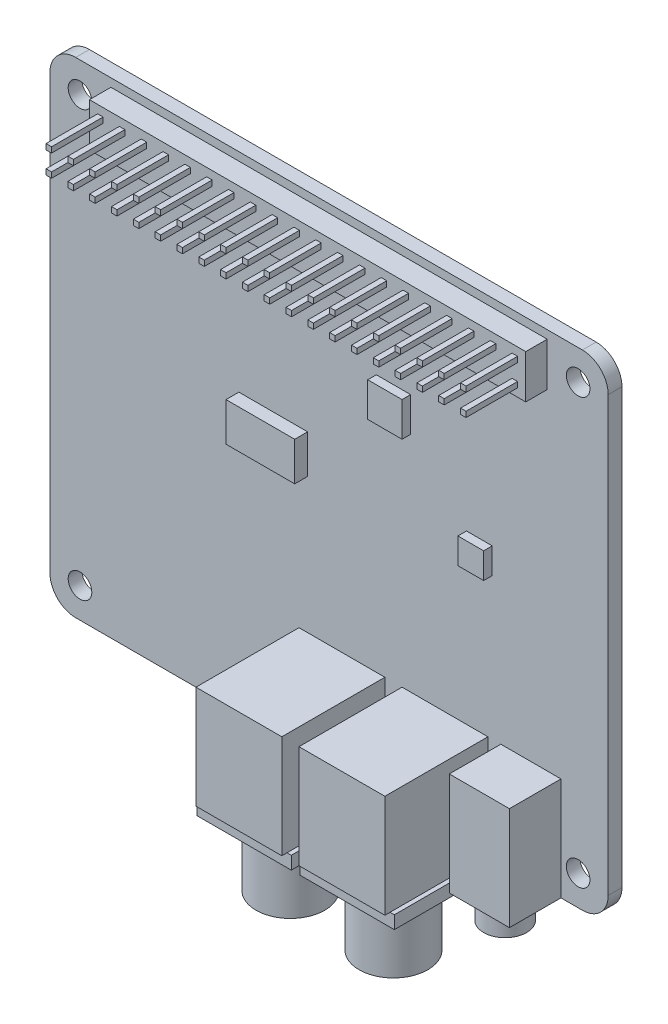
SolidWorks part; units mm, degrees
ref_plane "Front Plane" through (0, 0, 0) normal (0, 0, 1) x (1, 0, 0)
ref_plane "Top Plane" through (0, 0, 0) normal (0, 1, 0) x (1, 0, 0)
ref_plane "Right Plane" through (0, 0, 0) normal (1, 0, 0) x (0, 0, -1)
sketch "Sketch1" plane through (0, 0, 0) normal (0, 0, 1) x (1, 0, 0)
  line L0 (3, 0) -> (62, 0)
  line L1 (65, 3) -> (65, 53.5)
  line L2 (62, 56.5) -> (3, 56.5)
  line L3 (0, 53.5) -> (0, 3)
  arc A0 (62, 0) -> (65, 3) centre (62, 3) ccw
  arc A1 (65, 53.5) -> (62, 56.5) centre (62, 53.5) ccw
  arc A2 (3, 56.5) -> (0, 53.5) centre (3, 53.5) ccw
  arc A3 (0, 3) -> (3, 0) centre (3, 3) ccw
extrude "PCB" add sketch "Sketch1" along normal blind 1.6
ref_plane "Plane_z1_6" through (0, 0, 1.6) normal (0, 0, 1) x (1, 0, 0)
sketch "Sketch2" plane through (0, 0, 1.6) normal (0, 0, 1) x (1, 0, 0)
  line L1 (7.1, 50.46) -> (57.9, 50.46)
  line L2 (7.1, 50.46) -> (7.1, 55.54)
  line L3 (7.1, 55.54) -> (57.9, 55.54)
  line L4 (57.9, 50.46) -> (57.9, 55.54)
extrude "Header_Block" add sketch "Sketch2" along normal blind 2.5
ref_plane "Plane_z4_1" through (0, 0, 4.1) normal (0, 0, 1) x (1, 0, 0)
sketch "Sketch3" plane through (0, 0, 4.1) normal (0, 0, 1) x (1, 0, 0)
  line L1 (8.05, 51.41) -> (8.69, 51.41)
  line L2 (8.05, 51.41) -> (8.05, 52.05)
  line L3 (8.05, 52.05) -> (8.69, 52.05)
  line L4 (8.69, 51.41) -> (8.69, 52.05)
  line L6 (8.05, 53.95) -> (8.69, 53.95)
  line L7 (8.05, 53.95) -> (8.05, 54.59)
  line L8 (8.05, 54.59) -> (8.69, 54.59)
  line L9 (8.69, 53.95) -> (8.69, 54.59)
  line L11 (10.59, 51.41) -> (11.23, 51.41)
  line L12 (10.59, 51.41) -> (10.59, 52.05)
  line L13 (10.59, 52.05) -> (11.23, 52.05)
  line L14 (11.23, 51.41) -> (11.23, 52.05)
  line L16 (10.59, 53.95) -> (11.23, 53.95)
  line L17 (10.59, 53.95) -> (10.59, 54.59)
  line L18 (10.59, 54.59) -> (11.23, 54.59)
  line L19 (11.23, 53.95) -> (11.23, 54.59)
  line L21 (13.13, 51.41) -> (13.77, 51.41)
  line L22 (13.13, 51.41) -> (13.13, 52.05)
  line L23 (13.13, 52.05) -> (13.77, 52.05)
  line L24 (13.77, 51.41) -> (13.77, 52.05)
  line L26 (13.13, 53.95) -> (13.77, 53.95)
  line L27 (13.13, 53.95) -> (13.13, 54.59)
  line L28 (13.13, 54.59) -> (13.77, 54.59)
  line L29 (13.77, 53.95) -> (13.77, 54.59)
  line L31 (15.67, 51.41) -> (16.31, 51.41)
  line L32 (15.67, 51.41) -> (15.67, 52.05)
  line L33 (15.67, 52.05) -> (16.31, 52.05)
  line L34 (16.31, 51.41) -> (16.31, 52.05)
  line L36 (15.67, 53.95) -> (16.31, 53.95)
  line L37 (15.67, 53.95) -> (15.67, 54.59)
  line L38 (15.67, 54.59) -> (16.31, 54.59)
  line L39 (16.31, 53.95) -> (16.31, 54.59)
  line L41 (18.21, 51.41) -> (18.85, 51.41)
  line L42 (18.21, 51.41) -> (18.21, 52.05)
  line L43 (18.21, 52.05) -> (18.85, 52.05)
  line L44 (18.85, 51.41) -> (18.85, 52.05)
  line L46 (18.21, 53.95) -> (18.85, 53.95)
  line L47 (18.21, 53.95) -> (18.21, 54.59)
  line L48 (18.21, 54.59) -> (18.85, 54.59)
  line L49 (18.85, 53.95) -> (18.85, 54.59)
  line L51 (20.75, 51.41) -> (21.39, 51.41)
  line L52 (20.75, 51.41) -> (20.75, 52.05)
  line L53 (20.75, 52.05) -> (21.39, 52.05)
  line L54 (21.39, 51.41) -> (21.39, 52.05)
  line L56 (20.75, 53.95) -> (21.39, 53.95)
  line L57 (20.75, 53.95) -> (20.75, 54.59)
  line L58 (20.75, 54.59) -> (21.39, 54.59)
  line L59 (21.39, 53.95) -> (21.39, 54.59)
  line L61 (23.29, 51.41) -> (23.93, 51.41)
  line L62 (23.29, 51.41) -> (23.29, 52.05)
  line L63 (23.29, 52.05) -> (23.93, 52.05)
  line L64 (23.93, 51.41) -> (23.93, 52.05)
  line L66 (23.29, 53.95) -> (23.93, 53.95)
  line L67 (23.29, 53.95) -> (23.29, 54.59)
  line L68 (23.29, 54.59) -> (23.93, 54.59)
  line L69 (23.93, 53.95) -> (23.93, 54.59)
  line L71 (25.83, 51.41) -> (26.47, 51.41)
  line L72 (25.83, 51.41) -> (25.83, 52.05)
  line L73 (25.83, 52.05) -> (26.47, 52.05)
  line L74 (26.47, 51.41) -> (26.47, 52.05)
  line L76 (25.83, 53.95) -> (26.47, 53.95)
  line L77 (25.83, 53.95) -> (25.83, 54.59)
  line L78 (25.83, 54.59) -> (26.47, 54.59)
  line L79 (26.47, 53.95) -> (26.47, 54.59)
  line L81 (28.37, 51.41) -> (29.01, 51.41)
  line L82 (28.37, 51.41) -> (28.37, 52.05)
  line L83 (28.37, 52.05) -> (29.01, 52.05)
  line L84 (29.01, 51.41) -> (29.01, 52.05)
  line L86 (28.37, 53.95) -> (29.01, 53.95)
  line L87 (28.37, 53.95) -> (28.37, 54.59)
  line L88 (28.37, 54.59) -> (29.01, 54.59)
  line L89 (29.01, 53.95) -> (29.01, 54.59)
  line L91 (30.91, 51.41) -> (31.55, 51.41)
  line L92 (30.91, 51.41) -> (30.91, 52.05)
  line L93 (30.91, 52.05) -> (31.55, 52.05)
  line L94 (31.55, 51.41) -> (31.55, 52.05)
  line L96 (30.91, 53.95) -> (31.55, 53.95)
  line L97 (30.91, 53.95) -> (30.91, 54.59)
  line L98 (30.91, 54.59) -> (31.55, 54.59)
  line L99 (31.55, 53.95) -> (31.55, 54.59)
  line L101 (33.45, 51.41) -> (34.09, 51.41)
  line L102 (33.45, 51.41) -> (33.45, 52.05)
  line L103 (33.45, 52.05) -> (34.09, 52.05)
  line L104 (34.09, 51.41) -> (34.09, 52.05)
  line L106 (33.45, 53.95) -> (34.09, 53.95)
  line L107 (33.45, 53.95) -> (33.45, 54.59)
  line L108 (33.45, 54.59) -> (34.09, 54.59)
  line L109 (34.09, 53.95) -> (34.09, 54.59)
  line L111 (35.99, 51.41) -> (36.63, 51.41)
  line L112 (35.99, 51.41) -> (35.99, 52.05)
  line L113 (35.99, 52.05) -> (36.63, 52.05)
  line L114 (36.63, 51.41) -> (36.63, 52.05)
  line L116 (35.99, 53.95) -> (36.63, 53.95)
  line L117 (35.99, 53.95) -> (35.99, 54.59)
  line L118 (35.99, 54.59) -> (36.63, 54.59)
  line L119 (36.63, 53.95) -> (36.63, 54.59)
  line L121 (38.53, 51.41) -> (39.17, 51.41)
  line L122 (38.53, 51.41) -> (38.53, 52.05)
  line L123 (38.53, 52.05) -> (39.17, 52.05)
  line L124 (39.17, 51.41) -> (39.17, 52.05)
  line L126 (38.53, 53.95) -> (39.17, 53.95)
  line L127 (38.53, 53.95) -> (38.53, 54.59)
  line L128 (38.53, 54.59) -> (39.17, 54.59)
  line L129 (39.17, 53.95) -> (39.17, 54.59)
  line L131 (41.07, 51.41) -> (41.71, 51.41)
  line L132 (41.07, 51.41) -> (41.07, 52.05)
  line L133 (41.07, 52.05) -> (41.71, 52.05)
  line L134 (41.71, 51.41) -> (41.71, 52.05)
  line L136 (41.07, 53.95) -> (41.71, 53.95)
  line L137 (41.07, 53.95) -> (41.07, 54.59)
  line L138 (41.07, 54.59) -> (41.71, 54.59)
  line L139 (41.71, 53.95) -> (41.71, 54.59)
  line L141 (43.61, 51.41) -> (44.25, 51.41)
  line L142 (43.61, 51.41) -> (43.61, 52.05)
  line L143 (43.61, 52.05) -> (44.25, 52.05)
  line L144 (44.25, 51.41) -> (44.25, 52.05)
  line L146 (43.61, 53.95) -> (44.25, 53.95)
  line L147 (43.61, 53.95) -> (43.61, 54.59)
  line L148 (43.61, 54.59) -> (44.25, 54.59)
  line L149 (44.25, 53.95) -> (44.25, 54.59)
  line L151 (46.15, 51.41) -> (46.79, 51.41)
  line L152 (46.15, 51.41) -> (46.15, 52.05)
  line L153 (46.15, 52.05) -> (46.79, 52.05)
  line L154 (46.79, 51.41) -> (46.79, 52.05)
  line L156 (46.15, 53.95) -> (46.79, 53.95)
  line L157 (46.15, 53.95) -> (46.15, 54.59)
  line L158 (46.15, 54.59) -> (46.79, 54.59)
  line L159 (46.79, 53.95) -> (46.79, 54.59)
  line L161 (48.69, 51.41) -> (49.33, 51.41)
  line L162 (48.69, 51.41) -> (48.69, 52.05)
  line L163 (48.69, 52.05) -> (49.33, 52.05)
  line L164 (49.33, 51.41) -> (49.33, 52.05)
  line L166 (48.69, 53.95) -> (49.33, 53.95)
  line L167 (48.69, 53.95) -> (48.69, 54.59)
  line L168 (48.69, 54.59) -> (49.33, 54.59)
  line L169 (49.33, 53.95) -> (49.33, 54.59)
  line L171 (51.23, 51.41) -> (51.87, 51.41)
  line L172 (51.23, 51.41) -> (51.23, 52.05)
  line L173 (51.23, 52.05) -> (51.87, 52.05)
  line L174 (51.87, 51.41) -> (51.87, 52.05)
  line L176 (51.23, 53.95) -> (51.87, 53.95)
  line L177 (51.23, 53.95) -> (51.23, 54.59)
  line L178 (51.23, 54.59) -> (51.87, 54.59)
  line L179 (51.87, 53.95) -> (51.87, 54.59)
  line L181 (53.77, 51.41) -> (54.41, 51.41)
  line L182 (53.77, 51.41) -> (53.77, 52.05)
  line L183 (53.77, 52.05) -> (54.41, 52.05)
  line L184 (54.41, 51.41) -> (54.41, 52.05)
  line L186 (53.77, 53.95) -> (54.41, 53.95)
  line L187 (53.77, 53.95) -> (53.77, 54.59)
  line L188 (53.77, 54.59) -> (54.41, 54.59)
  line L189 (54.41, 53.95) -> (54.41, 54.59)
  line L191 (56.31, 51.41) -> (56.95, 51.41)
  line L192 (56.31, 51.41) -> (56.31, 52.05)
  line L193 (56.31, 52.05) -> (56.95, 52.05)
  line L194 (56.95, 51.41) -> (56.95, 52.05)
  line L196 (56.31, 53.95) -> (56.95, 53.95)
  line L197 (56.31, 53.95) -> (56.31, 54.59)
  line L198 (56.31, 54.59) -> (56.95, 54.59)
  line L199 (56.95, 53.95) -> (56.95, 54.59)
extrude "Header_Pins" add sketch "Sketch3" along normal blind 6
sketch "Sketch4" plane through (0, 0, 1.6) normal (0, 0, 1) x (1, 0, 0)
  line L1 (22, 27.75) -> (30, 27.75)
  line L2 (22, 27.75) -> (22, 32.25)
  line L3 (22, 32.25) -> (30, 32.25)
  line L4 (30, 27.75) -> (30, 32.25)
extrude "IC_DAC" add sketch "Sketch4" along normal blind 1.5
sketch "Sketch5" plane through (0, 0, 1.6) normal (0, 0, 1) x (1, 0, 0)
  line L1 (38, 38) -> (42, 38)
  line L2 (38, 38) -> (38, 42)
  line L3 (38, 42) -> (42, 42)
  line L4 (42, 38) -> (42, 42)
  line L6 (48.5, 28.5) -> (51.5, 28.5)
  line L7 (48.5, 28.5) -> (48.5, 31.5)
  line L8 (48.5, 31.5) -> (51.5, 31.5)
  line L9 (51.5, 28.5) -> (51.5, 31.5)
extrude "IC_Small" add sketch "Sketch5" along normal blind 1
sketch "Sketch6" plane through (0, 0, 1.6) normal (0, 0, 1) x (1, 0, 0)
  line L1 (29, 0) -> (39, 0)
  line L2 (29, 0) -> (29, 12)
  line L3 (29, 12) -> (39, 12)
  line L4 (39, 0) -> (39, 12)
  line L6 (41, 0) -> (51, 0)
  line L7 (41, 0) -> (41, 12)
  line L8 (41, 12) -> (51, 12)
  line L9 (51, 0) -> (51, 12)
extrude "RCA_Housings" add sketch "Sketch6" along normal blind 12
sketch "Sketch7" plane through (0, 0, 0) normal (0, 1, 0) x (1, 0, 0)
  line L1 (28.5, -1) -> (39.5, -1)
  line L2 (28.5, -1) -> (28.5, -13)
  line L3 (28.5, -13) -> (39.5, -13)
  line L4 (39.5, -1) -> (39.5, -13)
  line L6 (40.5, -1) -> (51.5, -1)
  line L7 (40.5, -1) -> (40.5, -13)
  line L8 (40.5, -13) -> (51.5, -13)
  line L9 (51.5, -1) -> (51.5, -13)
extrude "RCA_Flanges" add sketch "Sketch7" against normal blind 1.5
sketch "Sketch8" plane through (0, 0, 0) normal (0, 1, 0) x (1, 0, 0)
  circle A0 centre (34, -7.6) radius 4
  circle A1 centre (46, -7.6) radius 4
extrude "RCA_Barrels" add sketch "Sketch8" against normal blind 9
sketch "Sketch9" plane through (0, 0, 1.6) normal (0, 0, 1) x (1, 0, 0)
  line L1 (52.5, 0) -> (59.5, 0)
  line L2 (52.5, 0) -> (52.5, 12)
  line L3 (52.5, 12) -> (59.5, 12)
  line L4 (59.5, 0) -> (59.5, 12)
extrude "Jack_Body" add sketch "Sketch9" along normal blind 6
sketch "Sketch10" plane through (0, 0, 0) normal (0, 1, 0) x (1, 0, 0)
  circle A0 centre (56, -4.6) radius 2.5
extrude "Jack_Nose" add sketch "Sketch10" against normal blind 2.5
sketch "Sketch11" plane through (0, 0, 0) normal (0, 1, 0) x (1, 0, 0)
  circle A0 centre (34, -7.6) radius 2.5
  circle A1 centre (46, -7.6) radius 2.5
extrude "RCA_Bores" cut sketch "Sketch11" along normal blind 9
sketch "Sketch12" plane through (0, 0, 0) normal (0, 1, 0) x (1, 0, 0)
  circle A0 centre (56, -4.6) radius 1.75
extrude "Jack_Bore" cut sketch "Sketch12" along normal blind 2.5
sketch "Sketch13" plane through (0, 0, 0) normal (0, 0, 1) x (1, 0, 0)
  circle A0 centre (3.5, 3.5) radius 1.375
  circle A1 centre (3.5, 53) radius 1.375
  circle A2 centre (61.5, 3.5) radius 1.375
  circle A3 centre (61.5, 53) radius 1.375
extrude "Mount_Holes" cut sketch "Sketch13" against normal through all and the other way through all
equation "\"pcb_l\" = 65mm"
equation "\"pcb_w\" = 56.5mm"
equation "\"pcb_t\" = 1.6mm"
equation "\"pcb_r\" = 3mm"
equation "\"hole_d\" = 2.75mm"
equation "\"hole_inset\" = 3.5mm"
equation "\"hdr_pitch\" = 2.54mm"
equation "\"hdr_block_h\" = 2.5mm"
equation "\"hdr_pin\" = 0.64mm"
equation "\"hdr_pin_h\" = 6mm"
equation "\"rca_x1\" = 34mm"
equation "\"rca_x2\" = 46mm"
equation "\"rca_w\" = 10mm"
equation "\"rca_d\" = 12mm"
equation "\"rca_h\" = 12mm"
equation "\"rca_flange_w\" = 11mm"
equation "\"rca_flange_t\" = 1.5mm"
equation "\"rca_barrel_d\" = 8mm"
equation "\"rca_barrel_out\" = 9mm"
equation "\"rca_bore_d\" = 5mm"
equation "\"jack_x\" = 56mm"
equation "\"jack_w\" = 7mm"
equation "\"jack_d\" = 12mm"
equation "\"jack_h\" = 6mm"
equation "\"jack_nose_d\" = 5mm"
equation "\"jack_nose_out\" = 2.5mm"
equation "\"jack_bore_d\" = 3.5mm"
equation "\"D1@PCB\" = \"pcb_t\""
equation "\"D1@RCA_Barrels\" = \"rca_barrel_out\""
